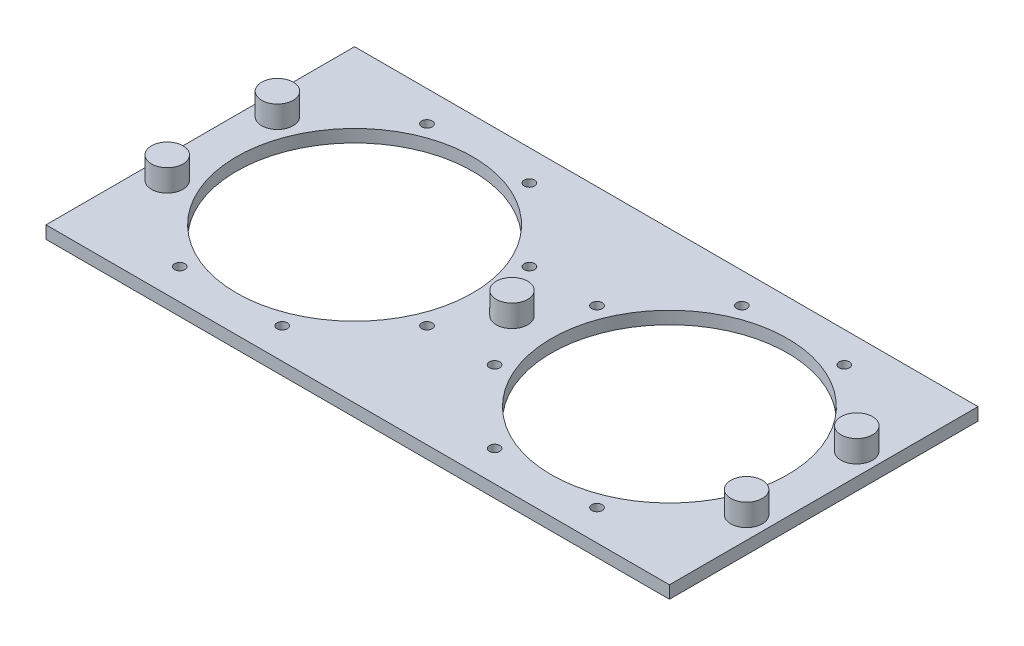
SolidWorks part; units mm, degrees
ref_plane "Front Plane" through (0, 0, 0) normal (0, 0, 1) x (1, 0, 0)
ref_plane "Top Plane" through (0, 0, 0) normal (0, 1, 0) x (1, 0, 0)
ref_plane "Right Plane" through (0, 0, 0) normal (1, 0, 0) x (0, 0, -1)
sketch "Sketch1" plane through (0, 0, 0) normal (0, 1, 0) x (1, 0, 0)
  circle A0 centre (-50, 0) radius 42.5 construction
  circle A1 centre (50, 0) radius 42.5 construction
  circle A2 centre (50, 0) radius 49 construction
  circle A3 centre (-50, 0) radius 49 construction
  circle A5 centre (-50, 0) radius 35.5 construction
  point P3 (58.7593, 0)
  point P8 (-55.9733, 0)
  dimension "D2" = 98
  dimension "D3" = 85
  dimension "D4" = 50
  dimension "D1" = 71
  dimension "D5" = 50
sketch "Sketch2" plane through (0, 0, 0) normal (0, 1, 0) x (1, 0, 0)
  line L1 (-99, -49) -> (99, -49)
  line L2 (-99, -49) -> (-99, 49)
  line L3 (-99, 49) -> (99, 49)
  line L4 (99, -49) -> (99, 49)
  line L5 (-99, -49) -> (99, 49) construction
  line L6 (-99, 49) -> (99, -49) construction
  circle A2 centre (-50, 0) radius 37.5
  circle A4 centre (50, 0) radius 37.5
  point P0 (0, 0)
  dimension "D1" = 98
  dimension "D3" = 75
  dimension "D2" = 198
extrude "Boss-Extrude1" add sketch "Sketch2" along normal blind 4
sketch "Sketch3" plane through (0, 4, 0) normal (0, 1, 0) x (1, 0, 0)
  line L0 (-50, 0) -> (-50, -42.5) construction
  line L1 (0, -2.2) -> (0, 2.2) construction
  circle A0 centre (-50, 0) radius 42.5 construction
  circle A1 centre (-66.264, -39.2649) radius 1.65
  circle A4 centre (-50, -42.5) radius 1 construction
  circle A5 centre (-66.264, 39.2649) radius 1.65
  circle A6 centre (-33.736, 39.2649) radius 1.65
  circle A7 centre (-10.7351, 16.264) radius 1.65
  circle A8 centre (-10.7351, -16.264) radius 1.65
  circle A9 centre (-33.736, -39.2649) radius 1.65
  circle A10 centre (10.7351, 16.264) radius 1.65
  circle A11 centre (33.736, 39.2649) radius 1.65
  circle A12 centre (66.264, 39.2649) radius 1.65
  circle A14 centre (10.7351, -16.264) radius 1.65
  circle A15 centre (33.736, -39.2649) radius 1.65
  circle A16 centre (66.264, -39.2649) radius 1.65
  circle A18 centre (-89.2649, -16.264) radius 1.65 [skipped]
  circle A19 centre (-89.2649, 16.264) radius 1.65 [skipped]
  point P26 (-50, 0)
  dimension "D1" = 3.3
  dimension "D2" = 2
  dimension "D6" = 45
  dimension "D3" = 22.5
  dimension "D5" = 45
  dimension "D4" = 8
extrude "Cut-Extrude1" cut sketch "Sketch3" against normal up to surface (4 mm away) up to face at (-50, 0, 37.5)
sketch "Sketch4" plane through (0, 4, 0) normal (0, 1, 0) x (1, 0, 0)
  line L0 (-92, 17.5) -> (-92, -17.5) construction
  line L1 (0, -2.2) -> (0, 2.2) construction
  circle A0 centre (-92, 17.5) radius 5
  circle A1 centre (-92, -17.5) radius 5
  circle A3 centre (-50, 0) radius 37.5 construction
  circle A4 centre (92, 17.5) radius 5
  circle A5 centre (92, -17.5) radius 5
  circle A6 centre (0, 0) radius 5
  point P4 (-92, 0)
  dimension "D1" = 10
  dimension "D3" = 35
  dimension "D4" = 42
  dimension "D5" = 35
extrude "Boss-Extrude2" add sketch "Sketch4" along normal blind 7
